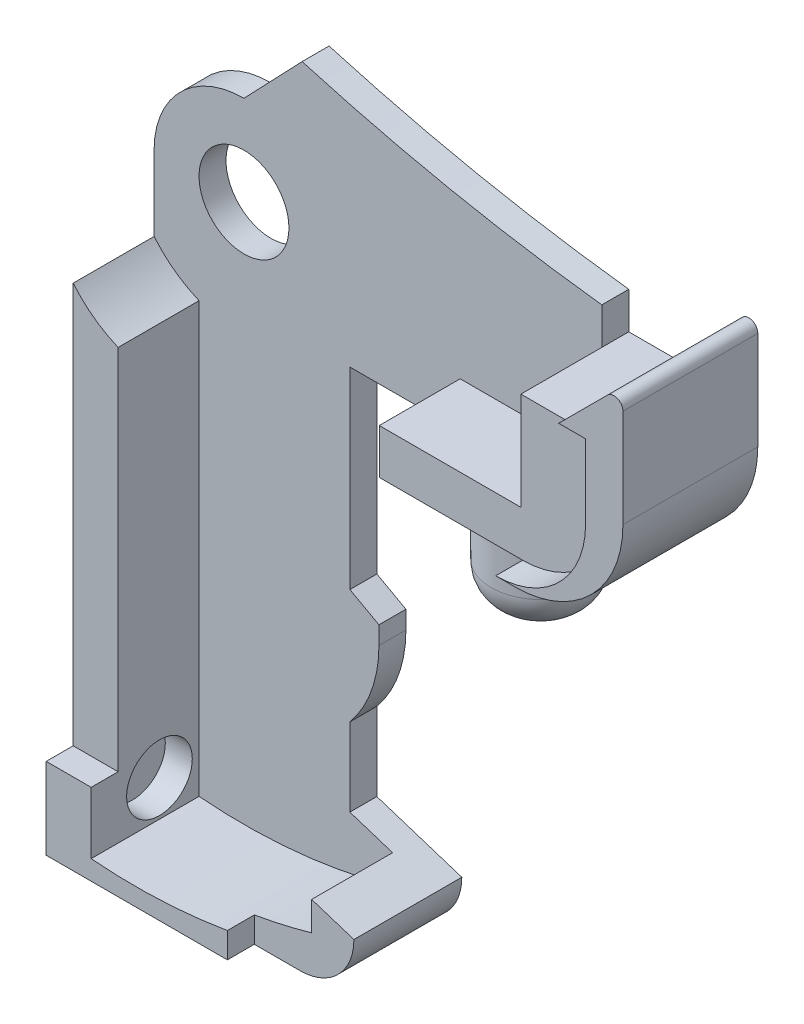
SolidWorks part; units mm, degrees
ref_plane "정면" through (0, 0, 0) normal (0, 0, 1) x (1, 0, 0)
ref_plane "윗면" through (0, 0, 0) normal (0, 1, 0) x (1, 0, 0)
ref_plane "우측면" through (0, 0, 0) normal (1, 0, 0) x (0, 0, -1)
sketch "스케치1" plane through (0, 0, 0) normal (0, 0, 1) x (1, 0, 0)
  line L0 (0, 5) -> (3.2319, 8.3833)
  line L1 (0, 5) -> (19.9, 5)
  line L2 (19.9, 5) -> (19.9, 2.9507)
  line L3 (19.9, 2.9507) -> (23.5, 2.9507)
  line L4 (23.5, 2.9507) -> (23.5, 4.0959)
  line L5 (23.5, 4.0959) -> (25, 4.0959)
  line L6 (25, 4.0959) -> (25, 0)
  line L7 (20, -5) -> (5.8894, -5)
  line L8 (5.8894, -5) -> (5.8894, -26.4376)
  line L9 (-5, -30.9618) -> (7.6137, -30.9618)
  line L10 (-5, -30.9618) -> (-5, 0)
  line L14 (19.9, 2.9507) -> (19.9, -2.5)
  line L15 (19.9, -2.5) -> (12.0232, -2.5)
  line L16 (-2.5, -4.3301) -> (-2.5, -26.4377)
  line L17 (-2.5, -29.8745) -> (-2.5, -26.4377)
  line L18 (-2.5, -26.4377) -> (-5, -26.4377)
  line L19 (5.0761, -29.546) -> (5.0761, -30.9618)
  line L20 (5.8894, -15.7188) -> (5.8894, -26.4376)
  line L21 (8.2649, -27.204) -> (8.2649, -28.8171)
  line L22 (12.0232, -2.5) -> (12.0232, -5)
  line L23 (5.8894, -15.7188) -> (5.8894, -26.4376)
  line L24 (7.5062, -17.6039) -> (7.5062, -16.6061)
  line L25 (7.5062, -16.6061) -> (5.8894, -15.7188)
  line L26 (23.5, 4.0959) -> (26.2222, 6.8181)
  line L27 (27.0757, 6.4645) -> (27.0757, 1)
  line L28 (21.0757, -5) -> (20, -5)
  line L29 (10.6137, -27.9618) -> (5.8894, -26.4376)
  circle A0 centre (0, 0) radius 2.5
  circle A1 centre (0, 0) radius 5
  arc A2 (-2.5, -29.8745) -> (8.2649, -28.8171) centre (0, 0) ccw
  arc A3 (-5, -4.1533) -> (-2.5, -6) centre (0, 0) ccw
  arc A4 (19.9, 5) -> (3.2319, 8.3833) centre (32.0341, 107.5303) cw
  arc A5 (25, 0) -> (20, -5) centre (20, 0) cw
  arc A6 (7.5062, -17.6039) -> (5.8894, -22.0908) centre (0.4717, -17.6039) cw
  arc A7 (7.6137, -30.9618) -> (10.6137, -27.9618) centre (7.6137, -27.9618) ccw
  arc A8 (27.0757, 1) -> (21.0757, -5) centre (21.0757, 1) cw
  arc A9 (26.2222, 6.8181) -> (27.0757, 6.4645) centre (26.5757, 6.4645) cw
  point P48 (27.0757, 7.6716)
  dimension "D1" = 5
  dimension "D3" = 5
  dimension "D6" = 3
  dimension "D9" = 6
  dimension "D10" = 0.5
  dimension "D4" = 30
  dimension "D5" = 1.5
  dimension "D7" = 5.0568
  dimension "D8" = 45
  dimension "D11" = 3.6
  dimension "D12" = 32.0757
extrude "보스-돌출3" add sketch "스케치1" along normal blind 7.5 contours A2 L17 L18 L10 L9 L19 | A9 L26 L5 L6 A5 L28 A8 L27 region at (-3.75, -26.5481, 0) region at (25.5751, 1.3496, 0)
extrude "보스-돌출4" add sketch "스케치1<7>" along normal blind 6 contours A2 L19 L9 | L15 L7 L6 L5 L4 L3 L14 | A1 L10 L18 L16 region at (20.1111, -1.5639, 0) region at (-3.7678, -15.8289, 0) region at (8.0449, -29.4837, 0)
sketch "스케치1<7>" plane through (0, 0, 0) normal (0, 0, 1) x (1, 0, 0) same geometry as "스케치1"
extrude "보스-돌출5" add sketch "스케치1<8>" along normal blind 1.5 contours L17 A2 L8 L15 L14 L2 L1 A1 L10 L18 | A1 A0 | L10 A3 L16 A1 | L1 A4 L0 | A6 L23 region at (7.1976, 6.0706, 0) region at (5.5582, -10.4694, 0) region at (3.4355, 3.4355, 0) region at (-3.8947, -3.9886, 0) region at (6.5659, -18.5308, 0)
sketch "스케치1<8>" plane through (0, 0, 0) normal (0, 0, 1) x (1, 0, 0) same geometry as "스케치1"
sketch "스케치2" plane through (0, -5, 0) normal (0, -1, 0) x (1, 0, 0)
  line L0 (20, 0) -> (5.8894, 0) construction
  circle A0 centre (18, 3) radius 2.75
  dimension "D1" = 5.5
  dimension "D2" = 3
extrude "보스-돌출6" add sketch "스케치2" along normal mid plane 4.9
sketch "스케치4" plane through (0, -7.45, 0) normal (0, -1, 0) x (1, 0, 0)
  circle A0 centre (18, 3) radius 2.75 construction
  circle A1 centre (18, 3) radius 2.75
extrude "보스-돌출7" add sketch "스케치4" along normal blind 2
sketch "스케치5" plane through (-2.5, 0, 0) normal (1, 0, 0) x (0, 0, -1)
  line L1 (-7.5, -29.8745) -> (-7.5, -26.4377) construction
  line L2 (-7.5, -29.8745) -> (-1.5, -29.8745) construction
  circle A0 centre (-3.7, -27.8745) radius 1.825
  dimension "D1" = 3.65
  dimension "D2" = 3.8
  dimension "D3" = 2
extrude "컷-돌출1" cut sketch "스케치5" against normal blind 1.5
fillet "필렛1" radius 2 1 edges at (18, -9.45, 0.25)
